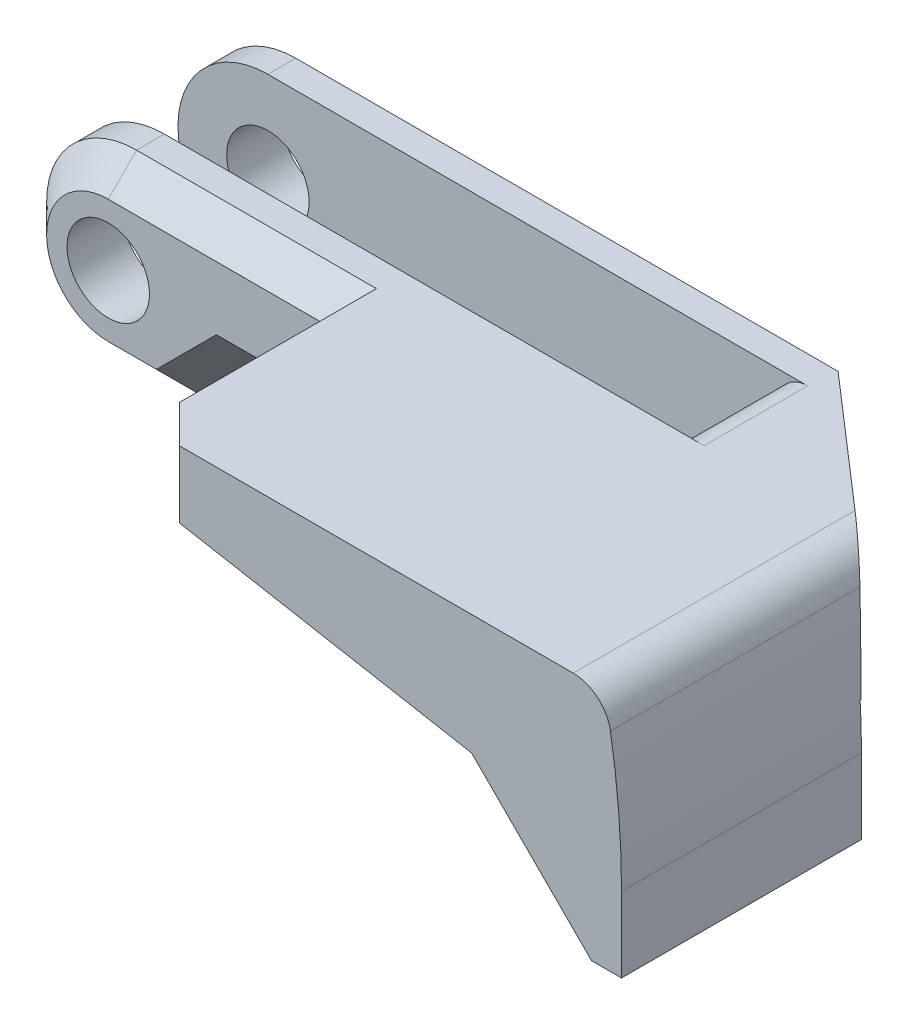
SolidWorks part; units mm, degrees
ref_plane "Front Plane" through (0, 0, 0) normal (0, 0, 1) x (1, 0, 0)
ref_plane "Top Plane" through (0, 0, 0) normal (0, 1, 0) x (1, 0, 0)
ref_plane "Right Plane" through (0, 0, 0) normal (1, 0, 0) x (0, 0, -1)
sketch "Sketch1" plane through (0, 0, 0) normal (0, 0, 1) x (1, 0, 0)
  line L0 (0, -4.7625) -> (3.175, -4.7625)
  line L1 (0, 4.7625) -> (38.1, 4.7625)
  line L2 (6.35, -1.5875) -> (30.1625, -1.5875)
  line L3 (3.175, -4.7625) -> (6.35, -1.5875)
  line L4 (38.1, 4.7625) -> (38.1, -7.9375)
  line L5 (38.1, -7.9375) -> (36.5125, -7.9375)
  line L6 (36.5125, -7.9375) -> (30.1625, -1.5875)
  arc A0 (0, 4.7625) -> (0, -4.7625) centre (0, 0) ccw
  dimension "D1" = 38.1
  dimension "D3" = 9.525
  dimension "D4" = 3.175
  dimension "D5" = 6.35
  dimension "D6" = 12.7
  dimension "D7" = 1.5875
extrude "Boss-Extrude1" add sketch "Sketch1" along normal blind 11.43
sketch "Sketch2" plane through (0, 0, 11.43) normal (0, 0, 1) x (1, 0, 0)
  line L0 (38.1, 4.7625) -> (0, 4.7625) construction
  line L1 (30.1625, -1.5875) -> (36.5125, -7.9375) construction
  line L2 (36.5125, -7.9375) -> (38.1, -7.9375) construction
  line L3 (38.1, -7.9375) -> (38.1, 4.7625) construction
  line L4 (6.35, -1.5875) -> (30.1625, -1.5875) construction
  line L5 (38.1, 4.7625) -> (12.7, 4.7625)
  line L6 (30.1625, -1.5875) -> (36.5125, -7.9375)
  line L7 (36.5125, -7.9375) -> (38.1, -7.9375)
  line L8 (38.1, -7.9375) -> (38.1, 4.7625)
  line L9 (12.7, -1.5875) -> (30.1625, -1.5875)
  line L10 (12.7, 4.7625) -> (12.7, -1.5875) construction
  line L11 (-4.7625, 0) -> (-4.7625, -7.9375) construction
  line L12 (37.2013, 4.7625) -> (38.1, 4.7625)
  line L13 (30.1625, -1.5875) -> (12.7, 1.5875)
  line L14 (12.7, 1.5875) -> (12.7, 4.7625)
  arc A1 (0, 4.7625) -> (0, -4.7625) centre (0, 0) ccw construction
  arc A2 (38.1, -3.9688) -> (37.2013, 4.7625) centre (-4.7625, -3.9687) ccw
  point P15 (-4.7625, -3.9687)
  dimension "D1" = 25.4
extrude "Boss-Extrude2" add sketch "Sketch2" along normal blind 12.7
sketch "Sketch3" plane through (38.1, 0, 0) normal (1, 0, 0) x (0, 0, -1)
  line L0 (0, -7.9375) -> (0, 4.7625) construction
  line L1 (0, -1.5875) -> (-11.43, -1.5875)
  line L2 (0, -1.5875) -> (0, -7.9375)
  line L3 (0, -7.9375) -> (-11.43, -7.9375)
  line L4 (-11.43, -1.5875) -> (-11.43, -7.9375)
  line L5 (-24.13, -7.9375) -> (0, -7.9375) construction
  dimension "D1" = 11.43
  dimension "D2" = 6.35
extrude "Cut-Extrude1" cut sketch "Sketch3" against normal blind 12.7
hole_wizard "11/64 (0.17188) Diameter Hole1" positions "Sketch9" profile "Sketch8" hole size "11/64" standard "ANSI Inch" end condition through all
sketch "Sketch9" plane through (0, 0, 11.43) normal (0, 0, 1) x (1, 0, 0)
  point P0 (0, 0)
sketch "Sketch8" plane through (0, 0, 11.43) normal (1, 0, 0) x (0, -1, 0)
  line L0 (0, 0) -> (0, 11.43)
  line L1 (0, 11.43) -> (2.1829, 11.43)
  line L2 (2.1829, 11.43) -> (2.1829, 0)
  line L5 (2.1829, 0) -> (0, 0)
  line L11 (0, -6.35) -> (0, 107.95) construction
  dimension "Thru Hole Dia." = 4.3658
  dimension "Thru Hole Depth" = 11.43
sketch "Sketch10" plane through (0, 4.7625, 0) normal (0, 1, 0) x (1, 0, 0)
  line L1 (38.1, 0) -> (0, 0) construction
  line L2 (26.9875, 0) -> (38.1, 0)
  line L3 (38.1, 0) -> (38.1, -9.652)
  line L6 (26.9875, 0) -> (38.1, -9.652)
  dimension "D1" = 11.1125
fillet "Fillet5" radius 2 1 edges
chamfer "Chamfer5" distance 1.5 angle 45 8 edges at (-4.7625, 0, 11.43) (1.5875, -4.7625, 11.43) (4.7625, -3.175, 11.43) (18.2563, -1.5875, 11.43) (19.05, 4.7625, 0) (1.5875, -4.7625, 0) (-4.7625, 0, 0)
sketch "Sketch12" plane through (0, 0, 11.43) normal (0, 0, -1) x (-1, 0, 0)
  line L4 (-38.1, -7.9375) -> (-36.5125, -7.9375)
  line L5 (-36.5125, -7.9375) -> (-30.1625, -1.5875)
  line L6 (-30.1625, -1.5875) -> (-38.0338, -1.5875)
  line L7 (-38.1, -3.9687) -> (-38.1, -7.9375)
  line L8 (-38.1, -7.9375) -> (-36.5125, -7.9375)
  line L9 (-36.5125, -7.9375) -> (-30.1625, -1.5875)
  line L10 (-30.1625, -1.5875) -> (-38.0338, -1.5875)
  line L11 (-38.1, -3.9687) -> (-38.1, -7.9375)
  arc A5 (-38.0338, -1.5875) -> (-38.1, -3.9687) centre (4.7625, -3.9687) ccw
  arc A8 (-38.0338, -1.5875) -> (-38.1, -3.9687) centre (4.7625, -3.9687) ccw
  dimension "D1" = 0
extrude "Boss-Extrude3" add sketch "Sketch12" along normal blind 1.778
sketch "Sketch14" plane through (0, 0, 11.43) normal (0, 0, 1) x (1, 0, 0)
  line L3 (38.0338, -1.5875) -> (38.1, -1.5875)
  line L4 (38.1, -1.5875) -> (38.1, 4.7625)
  line L5 (38.1, 4.7625) -> (35.5418, 4.7625)
  line L6 (38.0338, -1.5875) -> (38.1, -1.5875)
  line L7 (38.1, -1.5875) -> (38.1, 4.7625)
  line L8 (38.1, 4.7625) -> (35.5418, 4.7625)
  arc A2 (37.5144, 3.092) -> (35.5418, 4.7625) centre (35.5418, 2.7625) ccw
  arc A3 (38.0338, -1.5875) -> (37.5144, 3.092) centre (-4.7625, -3.9687) ccw
  arc A4 (37.5144, 3.092) -> (35.5418, 4.7625) centre (35.5418, 2.7625) ccw
  arc A5 (38.0338, -1.5875) -> (37.5144, 3.092) centre (-4.7625, -3.9687) ccw
  dimension "D1" = 0
extrude "Cut-Extrude8" cut sketch "Sketch14" against normal through all
sketch "Sketch15" plane through (0, 0, 24.13) normal (0, 0, 1) x (1, 0, 0)
  line L5 (35.5418, 4.7625) -> (12.7, 4.7625)
  line L6 (12.7, 4.7625) -> (12.7, 1.5875)
  line L7 (30.1625, -1.5875) -> (36.5125, -7.9375)
  line L8 (36.5125, -7.9375) -> (38.1, -7.9375)
  line L9 (38.1, -7.9375) -> (38.1, -3.9687)
  line L10 (35.5418, 4.7625) -> (12.7, 4.7625)
  line L11 (12.7, 4.7625) -> (12.7, 1.5875)
  line L12 (30.1625, -1.5875) -> (36.5125, -7.9375)
  line L13 (36.5125, -7.9375) -> (38.1, -7.9375)
  line L14 (38.1, -7.9375) -> (38.1, -3.9687)
  line L16 (12.7, 1.5875) -> (30.1625, -1.5875)
  line L17 (12.7, 1.5875) -> (30.1625, -1.5875)
  arc A5 (38.1, -3.9687) -> (37.5144, 3.092) centre (-4.7625, -3.9687) ccw
  arc A6 (37.5144, 3.092) -> (35.5418, 4.7625) centre (35.5418, 2.7625) ccw
  arc A10 (38.1, -3.9687) -> (37.5144, 3.092) centre (-4.7625, -3.9687) ccw
  arc A11 (37.5144, 3.092) -> (35.5418, 4.7625) centre (35.5418, 2.7625) ccw
  dimension "D1" = 0
extrude "Cut-Extrude9" cut sketch "Sketch15" against normal blind 1.778
extrude "Cut-Extrude10" cut sketch "Sketch10" against normal through all
sketch "Sketch16" plane through (0, 4.7625, 0) normal (0, 1, 0) x (1, 0, 0)
  line L0 (-4.7625, -5.715) -> (33.5673, -5.715) construction
  line L1 (-4.7625, -1.5) -> (-4.7625, -9.93) construction
  line L2 (28.7145, -1.5) -> (35.5418, -7.43) construction
  line L4 (-4.7625, -2.975) -> (26.9875, -2.975)
  line L5 (-4.7625, -2.975) -> (-4.7625, -8.455)
  line L6 (-4.7625, -8.455) -> (26.9875, -8.455)
  line L7 (26.9875, -2.975) -> (26.9875, -8.455)
  dimension "D1" = 31.75
  dimension "D2" = 5.48
extrude "Cut-Extrude11" cut sketch "Sketch16" against normal through all
fillet "Fillet7" radius 1.5875 2 edges at (26.9875, 4.7625, 5.715) (26.9875, -1.5875, 5.715)
sketch "Sketch18" plane through (0, 4.7625, 0) normal (0, 1, 0) x (1, 0, 0)
  line L0 (-4.7625, -1.5875) -> (46.0967, -1.5875) construction
  line L1 (0, 0) -> (26.9875, 0) construction
  dimension "D1" = 1.5875
ref_plane "Plane1" through (0, 0, 1.5875) normal (0, 0, -1) x (-1, 0, 0)
hole_wizard "1/8 (0.125) Diameter Hole1" positions "Sketch21" profile "Sketch19" hole size "1/8" standard "ANSI Inch"
sketch "Sketch21" plane through (0, 0, 1.5875) normal (0, 0, -1) x (-1, 0, 0)
  line L0 (-38.1, -3.9687) -> (-38.1, -7.9375) construction
  point P0 (-33.3375, 1.5875)
  dimension "D1" = 3.175
  dimension "D2" = 4.7625
sketch "Sketch19" plane through (33.3375, 1.5875, 1.5875) normal (1, 0, 0) x (0, 1, 0)
  line L0 (0, 0) -> (0, 20.0039)
  line L1 (0, 20.0039) -> (1.5875, 19.05)
  line L2 (1.5875, 19.05) -> (1.5875, 0)
  line L5 (1.5875, 0) -> (0, 0)
  line L10 (0, 20.0039) -> (-1.5875, 19.05) construction
  line L11 (0, -6.35) -> (0, 107.95) construction
  dimension "Hole Dia." = 3.175
  dimension "Hole Depth" = 19.05
  dimension "Drill Angle" = 118
chamfer "Chamfer6" distance 2 angle 45 1 edges at (12.7, 3.175, 22.352)
